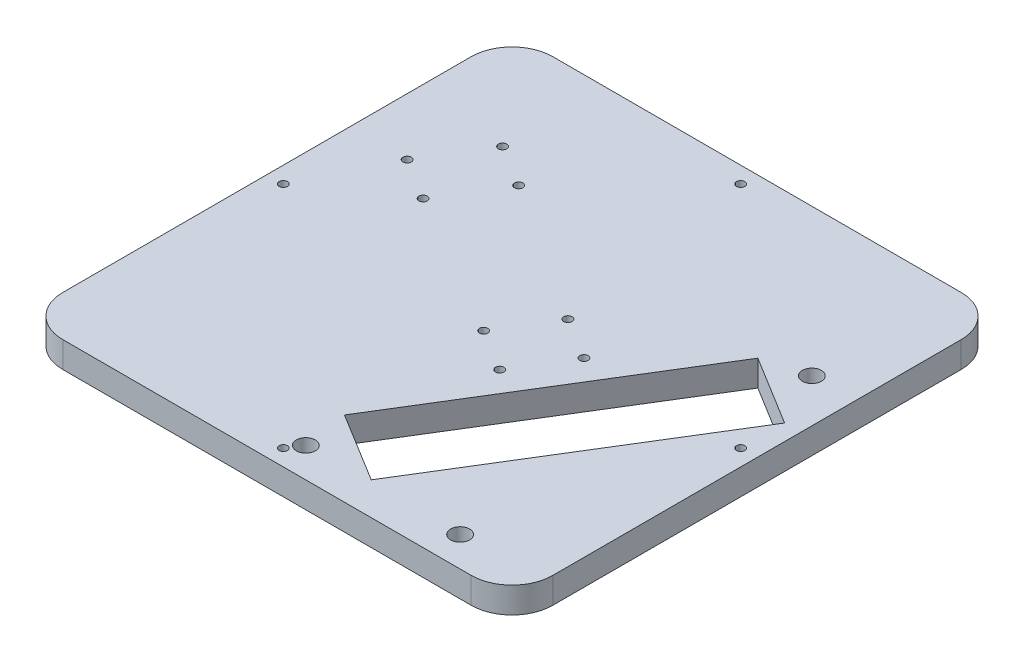
SolidWorks part; units mm, degrees
material "Beech"
ref_plane "Front Plane" through (0, 0, 0) normal (0, 0, 1) x (1, 0, 0)
ref_plane "Top Plane" through (0, 0, 0) normal (0, 1, 0) x (1, 0, 0)
ref_plane "Right Plane" through (0, 0, 0) normal (1, 0, 0) x (0, 0, -1)
sketch "Sketch1" plane through (0, 0, 0) normal (0, 1, 0) x (1, 0, 0)
  line L1 (10, 0) -> (110, 0)
  line L2 (0, 10) -> (0, 110)
  line L3 (10, 120) -> (110, 120)
  line L4 (120, 10) -> (120, 110)
  arc A0 (110, 0) -> (120, 10) centre (110, 10) ccw
  arc A1 (10, 0) -> (0, 10) centre (10, 10) cw
  arc A2 (0, 110) -> (10, 120) centre (10, 110) cw
  arc A3 (110, 120) -> (120, 110) centre (110, 110) cw
  point P7 (120, 0)
  point P10 (0, 0)
  point P13 (0, 120)
  point P16 (120, 120)
  dimension "D3" = 10
  dimension "D1" = 120
  dimension "D2" = 120
extrude "Boss-Extrude1" add sketch "Sketch1" along normal blind 6.35
sketch "Sketch2" plane through (0, 6.35, 0) normal (0, 1, 0) x (1, 0, 0)
  line L0 (58.0317, 5) -> (102.0317, 5) construction
  line L1 (102.0317, 5) -> (113, 94.33) construction
  line L2 (113, 94.33) -> (58.0317, 5) construction
  line L5 (60.4717, 18.5061) -> (77.5052, 8.0247)
  line L6 (77.5052, 8.0247) -> (116.0663, 70.6909)
  line L7 (116.0663, 70.6909) -> (99.0328, 81.1723)
  line L8 (60.4717, 18.5061) -> (99.0328, 81.1723)
  line L9 (10, 0) -> (110, 0) construction
  line L10 (120, 10) -> (120, 110) construction
  circle A0 centre (62.1922, 7.325) radius 2.325
  circle A1 centre (99.9747, 7.325) radius 2.325
  circle A2 centre (109.3931, 84.0319) radius 2.325
  dimension "D6" = 4.65
  dimension "D7" = 4.65
  dimension "D8" = 4.65
  dimension "D1" = 97
  dimension "D2" = 44
  dimension "D3" = 89.33
  dimension "D4" = 5
  dimension "D5" = 7
  dimension "D9" = 20
  dimension "D10" = 73.58
  dimension "D11" = 5
  dimension "D12" = 7.865
  dimension "D13" = 8.6209
extrude "Cut-Extrude1" cut sketch "Sketch2" against normal through all
sketch "Sketch5" plane through (0, 6.35, 0) normal (0, 1, 0) x (1, 0, 0)
  line L0 (79.7522, 49.8392) -> (0, 98.9139) construction
  line L1 (99.0328, 81.1723) -> (60.4717, 18.5061) construction
  line L2 (0, 110) -> (0, 10) construction
  line L3 (110, 120) -> (10, 120) construction
  line L4 (120, 10) -> (120, 110) construction
  line L5 (10, 0) -> (110, 0) construction
  circle A0 centre (69.86, 47.1201) radius 1.025
  circle A1 centre (59.6399, 53.409) radius 1.025
  circle A2 centre (77.721, 59.8952) radius 1.025
  circle A3 centre (67.5009, 66.1841) radius 1.025
  circle A4 centre (13.977, 80.333) radius 1.025
  circle A5 centre (24.1971, 74.0441) radius 1.025
  circle A6 centre (33.1063, 88.5226) radius 1.025
  circle A7 centre (22.8862, 94.8115) radius 1.025
  circle A8 centre (60, 116) radius 1.025
  circle A9 centre (60, 4) radius 1.025
  circle A10 centre (4, 60) radius 1.025
  circle A11 centre (116, 60) radius 1.025
  dimension "D2" = 2.05
  dimension "D3" = 2.05
  dimension "D4" = 2.05
  dimension "D5" = 2.05
  dimension "D14" = 2.05
  dimension "D15" = 2.05
  dimension "D16" = 2.05
  dimension "D17" = 2.05
  dimension "D26" = 2.05
  dimension "D27" = 2.05
  dimension "D28" = 2.05
  dimension "D29" = 2.05
  dimension "D1" = 90
  dimension "D6" = 7.5
  dimension "D7" = 7.5
  dimension "D8" = 7.5
  dimension "D9" = 7.5
  dimension "D10" = 7
  dimension "D11" = 7
  dimension "D12" = 12
  dimension "D13" = 12
  dimension "D18" = 8.5
  dimension "D19" = 8.5
  dimension "D20" = 8.5
  dimension "D21" = 8.5
  dimension "D22" = 60
  dimension "D23" = 60
  dimension "D24" = 12
  dimension "D25" = 12
  dimension "D30" = 4
  dimension "D31" = 4
  dimension "D32" = 4
  dimension "D33" = 4
  dimension "D34" = 60
  dimension "D35" = 60
  dimension "D36" = 60
  dimension "D37" = 60
extrude "Cut-Extrude2" cut sketch "Sketch5" against normal through all
sketch "Sketch4" plane through (0, 0, 0) normal (0, -1, 0) x (1, 0, 0)
  line L0 (79.7522, -49.8392) -> (96.7857, -39.3578) construction
  line L1 (99.0328, -81.1723) -> (60.4717, -18.5061) construction
  line L2 (77.5052, -8.0247) -> (116.0663, -70.6909) construction
sketch "Sketch6" plane through (0, 6.35, 0) normal (0, 1, 0) x (1, 0, 0)
  line L0 (79.7522, 49.8392) -> (96.7857, 39.3578) construction
